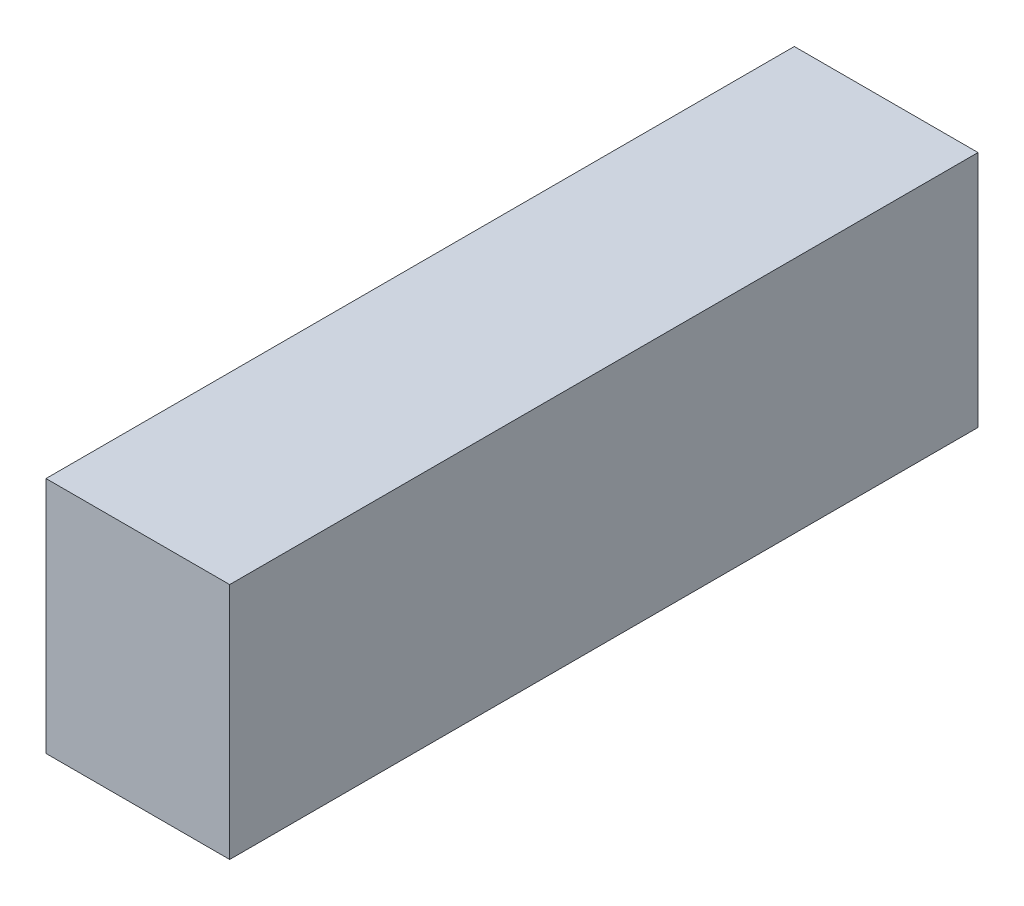
SolidWorks part; units mm, degrees
ref_plane "Front Plane" through (0, 0, 0) normal (0, 0, 1) x (1, 0, 0)
ref_plane "Top Plane" through (0, 0, 0) normal (0, 1, 0) x (1, 0, 0)
ref_plane "Right Plane" through (0, 0, 0) normal (1, 0, 0) x (0, 0, -1)
other "Bounding Box"
ref_plane "Default Plane" through (13.8565, 3.175, 6.7999) normal (0, -1, 0) x (-1, 0, 0)
sketch "Sketch1" plane through (0, 0, 0) normal (0, 1, 0) x (1, 0, 0)
  line L1 (-8.5725, -34.925) -> (8.5725, -34.925)
  line L2 (-8.5725, -34.925) -> (-8.5725, 34.925)
  line L3 (-8.5725, 34.925) -> (8.5725, 34.925)
  line L4 (8.5725, -34.925) -> (8.5725, 34.925)
  line L5 (-8.5725, -34.925) -> (8.5725, 34.925) construction
  line L6 (-8.5725, 34.925) -> (8.5725, -34.925) construction
  point P0 (0, 0)
  dimension "D1" = 69.85
  dimension "D2" = 17.145
extrude "Boss-Extrude1" add sketch "Sketch1" along normal mid plane 22.225
